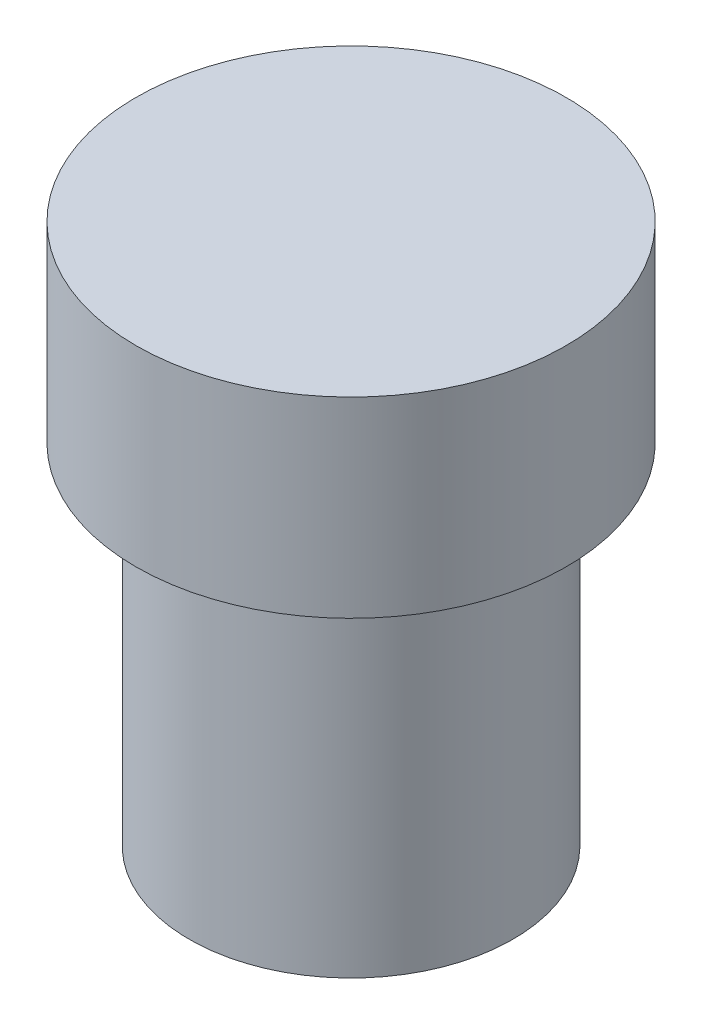
SolidWorks part; units mm, degrees
ref_plane "Front" through (0, 0, 0) normal (0, 0, 1) x (1, 0, 0)
ref_plane "Top" through (0, 0, 0) normal (0, 1, 0) x (1, 0, 0)
ref_plane "Right" through (0, 0, 0) normal (1, 0, 0) x (0, 0, -1)
sketch "Esboço1" plane through (0, 0, 0) normal (0, 1, 0) x (1, 0, 0)
  circle A0 centre (0, 0) radius 5.05
  point P2 (0, 0)
  point P4 (0, 0)
  dimension "D1" = 10.1
extrude "Ressalto-extrusão1" add sketch "Esboço1" along normal blind 4.5
sketch "Esboço2" plane through (0, 0, 0) normal (0, -1, 0) x (1, 0, 0)
  circle A0 centre (0, 0) radius 3.8
  point P2 (0, 0)
  dimension "D1" = 7.6
extrude "Ressalto-extrusão2" add sketch "Esboço2" along normal blind 8.2
